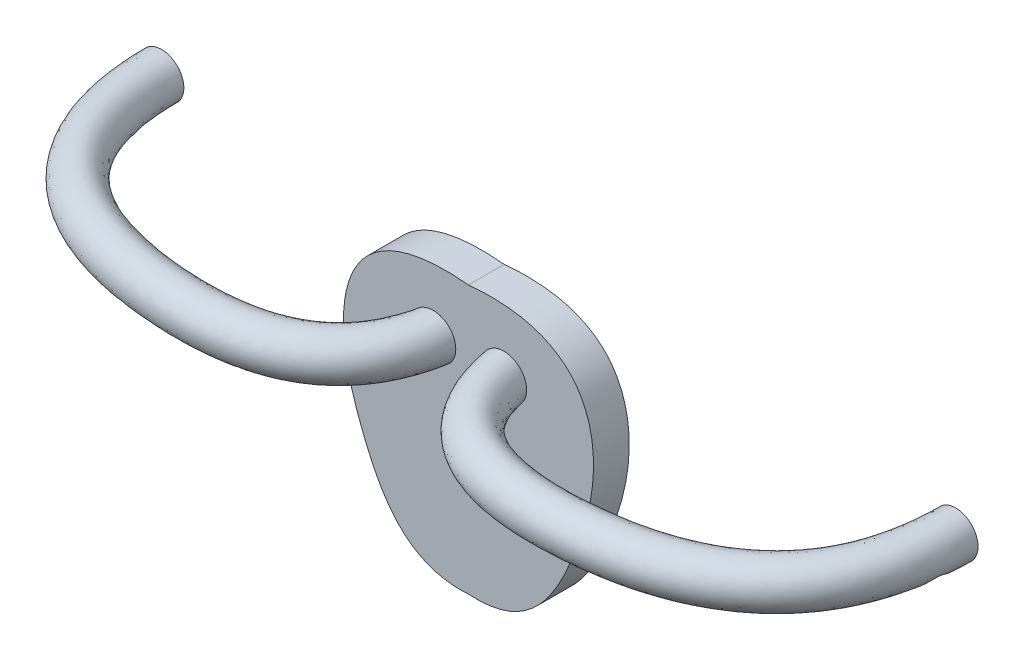
SolidWorks part; units mm, degrees
ref_plane "Front Plane" through (0, 0, 0) normal (0, 0, 1) x (1, 0, 0)
ref_plane "Top Plane" through (0, 0, 0) normal (0, 1, 0) x (1, 0, 0)
ref_plane "Right Plane" through (0, 0, 0) normal (1, 0, 0) x (0, 0, -1)
sketch "Sketch2" plane through (0, 0, 0) normal (0, 0, 1) x (1, 0, 0)
  line L0 (0, 69.4194) -> (0, -230.5806) construction
  spline S0 degree 3 poles (0, 69.4194) (-134.7181, 82.3039) (-155.0804, -27.6308) (-107.8831, -166.1792) (-69.5237, -235.4912) (0, -230.5806) knots 0 0 0 0 0.507485 0.634711 1 1 1 1
  spline S1 degree 3 poles (0, 69.4194) (134.7181, 82.3039) (155.0804, -27.6308) (107.8831, -166.1792) (69.5237, -235.4912) (0, -230.5806) knots 0 0 0 0 0.507485 0.634711 1 1 1 1
  point P4 (-166.8077, 137.9248)
  point P6 (-202.9828, 35.8305)
  point P8 (-168.4154, 77.6329)
  point P10 (-182.8855, 36.6344)
  point P11 (-114.5547, -188.4555)
  point P12 (-150.7298, -125.7519)
  point P13 (-189.3166, -13.207)
  point P14 (-167.6116, 39.046)
  point P19 (-170.53, -19.9281)
  point P20 (-137.9449, 28.2412)
  point P21 (-118.1105, -133.2676)
  point P22 (-84.1087, -195.6043)
  point P23 (-135.1114, -79.4314)
  point P24 (-139.3617, -19.9281)
  dimension "D1" = 300
extrude "Boss-Extrude1" add sketch "Sketch2" along normal mid plane 40
sketch "Sketch27" plane through (0, 0, 0) normal (0, 1, 0) x (1, 0, 0)
  spline S0 degree 3 poles (37.663, -7.6459) (52.0598, -117.5229) (260.0413, -158.9534) (444.3371, -72.6613) (445.0126, 81.0148) knots 0 0 0 0 0.426199 1 1 1 1
  point P2 (511.5932, -120.1629)
  point P4 (739.4235, -57.265)
  point P6 (880.5944, 206.9064)
  point P8 (228.7825, -130.9522)
  point P9 (568.0478, 205.6417)
  point P10 (478.5566, -66.8391)
  point P11 (459.6352, -74.0903)
  point P12 (416.5303, -84.8666)
  point P13 (547.3893, 147.9533)
  point P14 (134.4339, -131.3667)
  point P15 (487.1084, 77.1696)
  point P16 (337.2357, -103.6823)
  point P17 (225.0405, -129.6379)
  point P18 (114.5199, -116.2415)
  point P19 (445.0126, 81.0148)
sweep "Sweep2" add path "Sketch27" circular profile diameter 50 parameters "D3"=50
mirror "Mirror2" about plane through (0, 0, 0) normal (1, 0, 0) of "Sweep2"
sketch "Sketch102" plane through (0, 0, 0) normal (0, 1, 0) x (1, 0, 0)
  line L0 (0, 0) -> (0, 139.9306) construction
  circle A0 centre (444.5528, 46.1966) radius 20
  circle A1 centre (-444.5528, 46.1966) radius 20
  dimension "D1" = 40
extrude "Cut-Extrude2" cut sketch "Sketch102" against normal blind 30 and the other way blind 1
